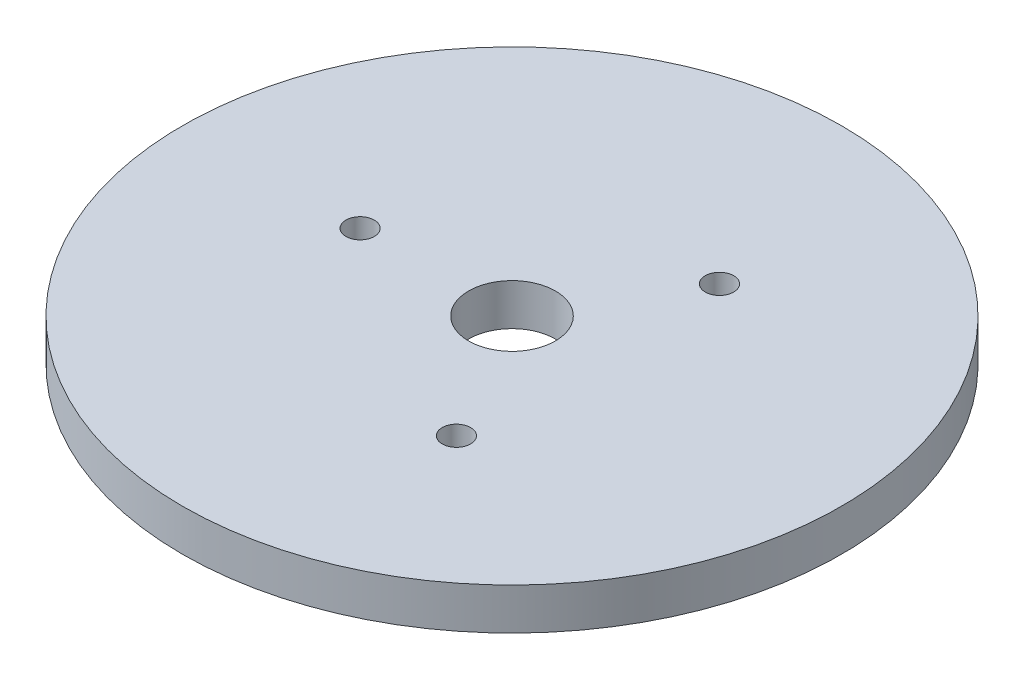
SolidWorks part; units mm, degrees
ref_plane "Front Plane" through (0, 0, 0) normal (0, 0, 1) x (1, 0, 0)
ref_plane "Top Plane" through (0, 0, 0) normal (0, 1, 0) x (1, 0, 0)
ref_plane "Right Plane" through (0, 0, 0) normal (1, 0, 0) x (0, 0, -1)
sketch "Sketch1" plane through (0, 0, 0) normal (0, 1, 0) x (1, 0, 0)
  circle A0 centre (0, 0) radius 95
  dimension "FLANGE_OD" = 190
extrude "Boss-Extrude1" add sketch "Sketch1" along normal blind 12
sketch "Sketch2" plane through (0, 0, 0) normal (0, 1, 0) x (1, 0, 0)
  circle A0 centre (0, 0) radius 12.5
  dimension "BORE_D" = 25
extrude "Cut-Extrude1" cut sketch "Sketch2" along normal through all
sketch "Sketch3" plane through (0, 12, 0) normal (0, 1, 0) x (1, 0, 0)
  circle A0 centre (0, 0) radius 43.7813 construction
  circle A1 centre (-43.7813, 0) radius 4.0974
  dimension "BOLT_D" = 8.1948
  dimension "BOLT_PCD" = 87.5626
extrude "Cut-Extrude2" cut sketch "Sketch3" against normal blind 8.4743
pattern_circular "CirPattern1" count 3 over 360 about axis through (0, 0, 0) along (0, 1, 0) of "Cut-Extrude2"
